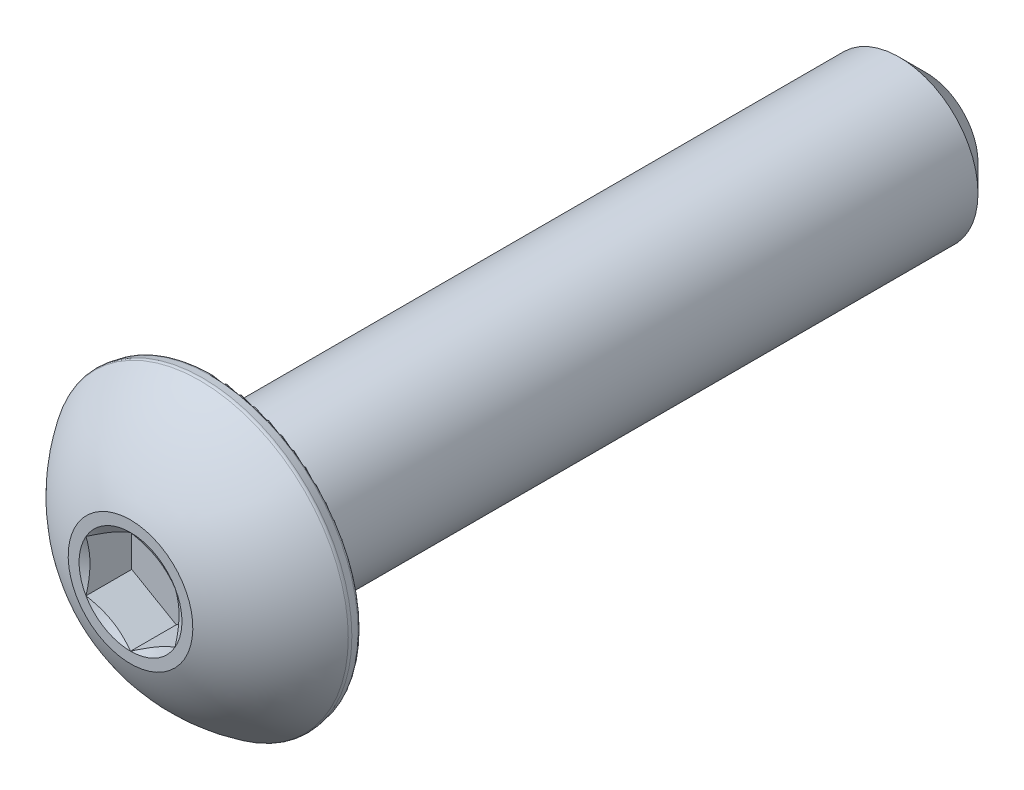
SolidWorks part; units mm, degrees
ref_plane "Front Plane" through (0, 0, 0) normal (0, 0, 1) x (1, 0, 0)
ref_plane "Top Plane" through (0, 0, 0) normal (0, 1, 0) x (1, 0, 0)
ref_plane "Right Plane" through (0, 0, 0) normal (1, 0, 0) x (0, 0, -1)
sketch "Sketch1" plane through (0, 0, 0) normal (1, 0, 0) x (0, 0, -1)
  line L0 (-8.8646, 0) -> (8.8646, 0) construction
  line L1 (-8.8646, 0) -> (-8.8646, 3.3274)
  line L2 (-8.8646, 3.3274) -> (-7.0104, 3.3274)
  line L3 (-7.0104, 3.3274) -> (-7.0104, 1.7526)
  line L4 (-7.0104, 1.7526) -> (8.8646, 1.7526)
  line L5 (8.8646, 1.7526) -> (8.8646, 0)
  point P2 (0, 0)
  point P4 (8.0709, 0)
  point P9 (7.674, 1.7526)
  point P10 (7.674, -1.7526)
  point P11 (8.8646, -1.7526)
  point P15 (-7.8448, 0)
  dimension "Head Height" = 1.8542
  dimension "Head Diameter" = 6.6548
  dimension "Length" = 15.875
  dimension "Screw Size Decimal Equivalent" = 3.5052
  dimension "Thread Pitch" = 0.7937
  dimension "D1" = 1.1906
  dimension "D2" = 1.0198
sketch "Sketch2" plane through (0, 0, 0) normal (0, 0, 1) x (1, 0, 0)
  line L0 (0, 1.7526) -> (0, 0) construction
  line L1 (0, 1.1457) -> (-0.9922, 0.5728)
  line L2 (-0.9922, 0.5728) -> (-0.9922, -0.5728)
  line L3 (-0.9922, -0.5728) -> (0, -1.1457)
  line L4 (0, -1.1457) -> (0.9922, -0.5728)
  line L5 (0.9922, -0.5728) -> (0.9922, 0.5728)
  line L6 (0.9922, 0.5728) -> (0, 1.1457)
  circle A0 centre (0, 0) radius 0.9922 construction
  circle A1 centre (0, 0) radius 1.3891
  point P10 (0, 1.3891)
  dimension "D1" = 2.7781
  dimension "Drive Size" = 1.9844
sketch "Sketch3" plane through (0, 0, 0) normal (1, 0, 0) x (0, 0, -1)
  line L0 (-8.8646, 0) -> (-8.8646, 1.3891)
  line L1 (-8.8646, 0) -> (-8.8646, 3.3274) construction
  line L2 (-8.8646, 3.3274) -> (-7.0104, 3.3274) construction
  line L3 (-7.2885, 3.3274) -> (-7.0104, 3.2784)
  line L4 (-7.0104, 3.3274) -> (-7.0104, 1.7526) construction
  line L5 (-7.0104, 3.2784) -> (-7.0104, 1.7526)
  line L6 (-8.8646, 0) -> (8.8646, 0) construction
  line L7 (-8.8646, 0) -> (8.8646, 0)
  line L8 (8.8646, 0) -> (8.8646, 1.1573)
  line L9 (8.8646, 1.7526) -> (8.8646, 0) construction
  line L10 (8.8646, 1.1573) -> (8.2693, 1.7526)
  line L11 (-7.0104, 1.7526) -> (8.8646, 1.7526) construction
  line L12 (8.2693, 1.7526) -> (-7.0104, 1.7526)
  arc A0 (-8.8646, 1.3891) -> (-7.2885, 3.3274) centre (-5.1763, 0) cw
  dimension "D1" = 0.2781
  dimension "D2" = 10
  dimension "D3" = 45
  dimension "D4" = 0.5953
revolve "Revolve1" add sketch "Sketch3" angle 360 about L7
sketch "Sketch4" plane through (0, 0, 8.8646) normal (0, 0, 1) x (1, 0, 0)
  line L0 (-0.9922, -0.5728) -> (0, -1.1457) construction
  line L1 (-0.9922, 0.5728) -> (-0.9922, -0.5728) construction
  line L2 (0, 1.1457) -> (-0.9922, 0.5728) construction
  line L3 (0.9922, 0.5728) -> (0, 1.1457) construction
  line L4 (0.9922, -0.5728) -> (0.9922, 0.5728) construction
  line L5 (0, -1.1457) -> (0.9922, -0.5728) construction
  line L6 (-0.9922, -0.5728) -> (0, -1.1457)
  line L7 (-0.9922, 0.5728) -> (-0.9922, -0.5728)
  line L8 (0, 1.1457) -> (-0.9922, 0.5728)
  line L9 (0.9922, 0.5728) -> (0, 1.1457)
  line L10 (0.9922, -0.5728) -> (0.9922, 0.5728)
  line L11 (0, -1.1457) -> (0.9922, -0.5728)
extrude "Cut-Extrude1" cut sketch "Sketch4" against normal up to vertex (1.0198 mm away) up to point (0, 0, 7.8448)
sketch "Sketch5" plane through (0, 0, 8.8646) normal (0, 0, 1) x (1, 0, 0)
  circle A0 centre (0, 0) radius 1.1457
extrude "Cut-Extrude2" cut sketch "Sketch5" against normal up to vertex (1.0198 mm away) draft 60 up to point (0, 0, 7.8448)
fillet "Fillet1" radius 0.0927 2 edges at (3.3274, 0, 7.2885) (3.2784, 0, 7.0104)
split "Split1" [suppressed] bodies to split 106
sketch "Sketch6" [suppressed] plane through (0, 0, -8.8646) normal (0, 0, -1) x (-1, 0, 0)
  circle A0 centre (0, 0) radius 1.7526 construction
  circle A1 centre (0, 0) radius 1.7526
curve "Helix/Spiral1" [suppressed] pitch 0.7937 height 16.6687 turns 21
sketch "Sketch7" [suppressed] plane through (0, 0, 0) normal (1, 0, 0) x (0, 0, -1)
  line L0 (8.815, 1.8385) -> (9.2119, 1.1511) construction
  line L1 (9.2119, 1.1511) -> (9.6087, 1.8385) construction
  line L2 (9.6087, 1.8385) -> (8.815, 1.8385) construction
  line L3 (8.8398, 1.7956) -> (9.5839, 1.7956)
  line L4 (9.5839, 1.7956) -> (9.2615, 1.237)
  line L5 (9.2615, 1.237) -> (9.1623, 1.237)
  line L6 (9.1623, 1.237) -> (8.8398, 1.7956)
  line L7 (9.2119, 1.237) -> (9.2119, 1.1511) construction
  line L8 (8.8646, 1.7526) -> (9.5591, 1.7526) construction
  line L9 (9.2119, 1.8385) -> (9.2119, 1.7526) construction
  point P12 (9.2119, 1.7956)
  dimension "D1" = 0.7937
  dimension "D2" = 0.0992
sweep "Cut-Sweep1" [suppressed] cut profiles "Sketch7" path "Helix/Spiral1"
sketch "Sketch8" [suppressed] plane through (0, 0, 7.0104) normal (0, 0, -1) x (-1, 0, 0)
  circle A0 centre (0, 0) radius 1.8385
extrude "Boss-Extrude1" [suppressed] add sketch "Sketch8" along normal up to vertex draft 45 up to point (0, 1.7526, -7.674)
equation "\"D1@Sketch1\"=\"Thread Pitch@Sketch1\"*1.5"
equation "\"D2@Sketch1\"=0.55*\"Head Height@Sketch1\""
equation "\"D1@Sketch2\"=\"Drive Size@Sketch2\"*1.4"
equation "\"D1@Sketch3\"=0.15*\"Head Height@Sketch1\""
equation "\"D4@Sketch3\"=0.75*\"Thread Pitch@Sketch1\""
equation "\"D1@Fillet1\"=.05*\"Head Height@Sketch1\""
equation "\"D4@Helix/Spiral1\"=\"Thread Pitch@Sketch1\""
equation "\"D3@Helix/Spiral1\"=\"Length@Sketch1\"+\"Thread Pitch@Sketch1\""
equation "\"D2@Sketch7\"=\"D1@Sketch7\"/8"
equation "\"D1@Sketch7\"=\"Thread Pitch@Sketch1\""
